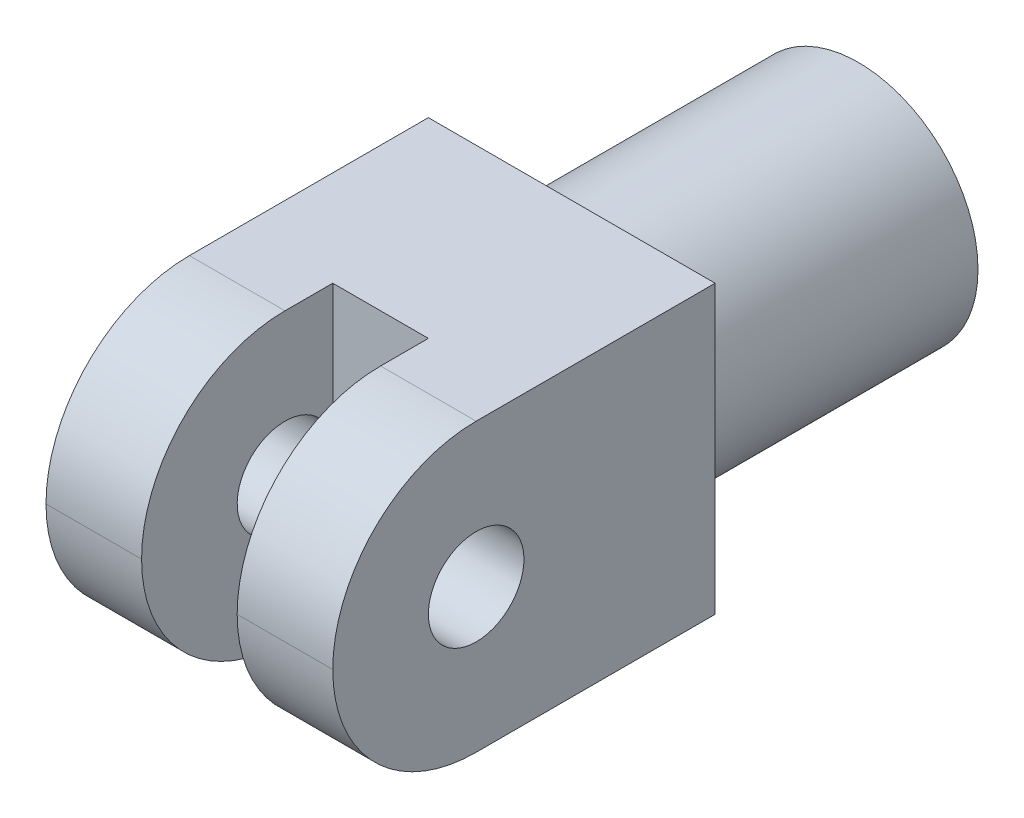
SolidWorks part; units mm, degrees
ref_plane "Front Plane" through (0, 0, 0) normal (0, 0, 1) x (1, 0, 0)
ref_plane "Top Plane" through (0, 0, 0) normal (0, 1, 0) x (1, 0, 0)
ref_plane "Right Plane" through (0, 0, 0) normal (1, 0, 0) x (0, 0, -1)
sketch "Sketch2" plane through (0, 0, 0) normal (0, 0, 1) x (1, 0, 0)
  circle A0 centre (0, 0) radius 12.5
  dimension "D1" = 25
extrude "Boss-Extrude1" add sketch "Sketch2" along normal blind 30
sketch "Sketch3" plane through (0, 0, 30) normal (0, 0, 1) x (1, 0, 0)
  line L1 (-15, 15) -> (15, 15)
  line L2 (-15, 15) -> (-15, -15)
  line L3 (-15, -15) -> (15, -15)
  line L4 (15, 15) -> (15, -15)
  line L5 (-15, 15) -> (15, -15) construction
  line L6 (-15, -15) -> (15, 15) construction
  point P0 (0, 0)
  dimension "D1" = 30
  dimension "D2" = 30
extrude "Boss-Extrude2" add sketch "Sketch3" along normal blind 40
sketch "Sketch4" plane through (0, 15, 0) normal (0, 1, 0) x (1, 0, 0)
  line L0 (5, -70) -> (5, -50)
  line L1 (15, -70) -> (-15, -70) construction
  line L2 (5, -50) -> (-5, -50)
  line L3 (-5, -50) -> (-5, -70)
  line L4 (15, -70) -> (15, -30) construction
  line L5 (-15, -70) -> (-15, -30) construction
  line L6 (5, -70) -> (-5, -70)
  dimension "D1" = 10
  dimension "D2" = 10
  dimension "D3" = 20
extrude "Cut-Extrude1" cut sketch "Sketch4" against normal blind 40
fillet "Fillet1" radius 15 4 edges at (10, 15, 70) (10, -15, 70) (-10, -15, 70) (-10, 15, 70)
sketch "Sketch5" plane through (-15, 0, 0) normal (-1, 0, 0) x (0, 0, 1)
  circle A0 centre (55, 0) radius 5
  dimension "D1" = 10
extrude "Cut-Extrude2" cut sketch "Sketch5" against normal blind 40
